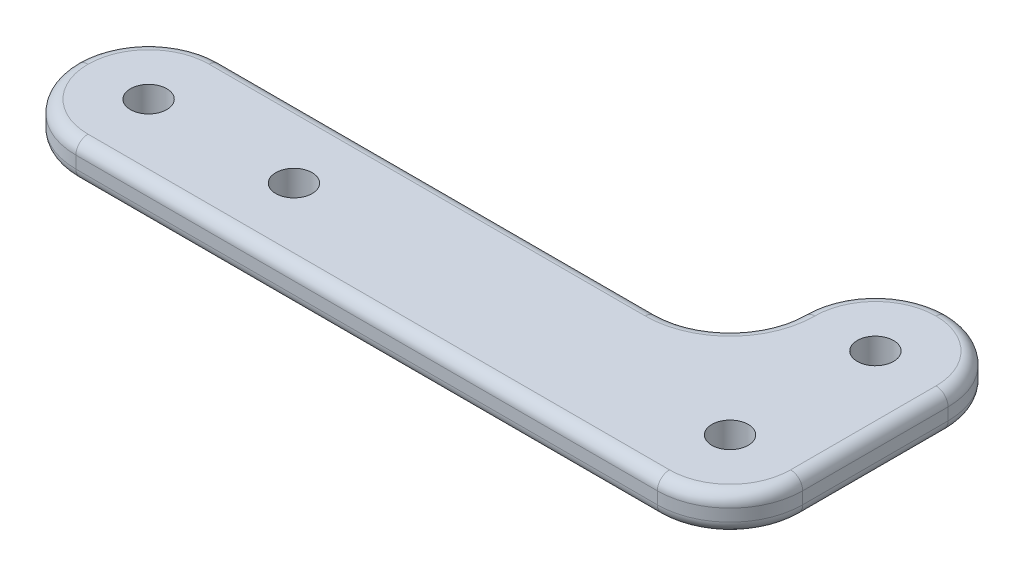
SolidWorks part; units mm, degrees
material "6061 Alloy"
ref_plane "Front Plane" through (0, 0, 0) normal (0, 0, 1) x (1, 0, 0)
ref_plane "Top Plane" through (0, 0, 0) normal (0, 1, 0) x (1, 0, 0)
ref_plane "Right Plane" through (0, 0, 0) normal (1, 0, 0) x (0, 0, -1)
sketch "Sketch1" plane through (0, 0, 0) normal (0, 1, 0) x (1, 0, 0)
  line L0 (0, 25.4) -> (0, -25.4) construction
  line L1 (-12.7, -25.4) -> (12.7, -25.4) construction
  line L2 (-12.7, -25.4) -> (-12.7, 25.4) construction
  line L3 (-12.7, 25.4) -> (12.7, 25.4)
  line L4 (12.7, -25.4) -> (12.7, 25.4) construction
  line L5 (-12.7, -25.4) -> (12.7, 25.4) construction
  line L6 (-12.7, 25.4) -> (12.7, -25.4) construction
  line L7 (-12.7, 0) -> (-114.3, 0)
  line L8 (-114.3, 0) -> (-114.3, -25.4)
  line L9 (-114.3, -25.4) -> (-12.7, -25.4)
  line L10 (-114.3, -12.7) -> (0, -12.7)
  line L11 (-12.7, -25.4) -> (0, -25.4)
  line L12 (12.7, -12.7) -> (12.7, 25.4)
  line L13 (-12.7, 0) -> (-12.7, 25.4)
  circle A1 centre (0, -12.7) radius 3.175
  circle A2 centre (0, 12.7) radius 3.175
  circle A4 centre (0, -12.7) radius 12.7
  circle A5 centre (-101.6, -12.7) radius 3.175
  circle A6 centre (-76.2, -12.7) radius 3.175
  point P0 (0, 0)
  dimension "D3" = 6.35
  dimension "D1" = 25.4
  dimension "D8" = 12.7
  dimension "D6" = 76.2
  dimension "D2" = 25.4
  dimension "D4" = 25.4
  dimension "D5" = 90
  dimension "D7" = 12.7
  dimension "D9" = 25.4
extrude "Boss-Extrude1" add sketch "Sketch1" along normal blind 6.35 contours A5 L10 A4 L12 L3 L13 L7 L8 A2 | A4 A1 | A5 L10 L8 L9 L11 A4 region at (-40.7547, 0, 0.1231) region at (8.7263, 0, 21.4263) region at (-61.4425, 0, 19.2665)
fillet "Fillet2" radius 12.7 5 edges at (12.7, 3.175, -25.4) (-12.7, 3.175, -25.4) (-114.3, 3.175, 0) (-114.3, 3.175, 25.4) (-12.7, 3.175, 0)
fillet "Fillet3" radius 2.1167 18 edges at (-8.9803, 0, -21.6803) (8.9803, 0, -21.6803) (12.7, 0, 0) (8.9803, 0, 21.6803) (-50.8, 0, 25.4) (-110.5803, 0, 21.6803) (-110.5803, 0, 3.7197) (-8.9803, 6.35, -21.6803) (8.9803, 6.35, -21.6803) (12.7, 6.35, 0) (8.9803, 6.35, 21.6803) (-50.8, 6.35, 25.4) (-110.5803, 6.35, 21.6803) (-110.5803, 6.35, 3.7197) (-63.5, 0, 0) (-63.5, 6.35, 0) (-16.4197, 0, -3.7197) (-16.4197, 6.35, -3.7197)
